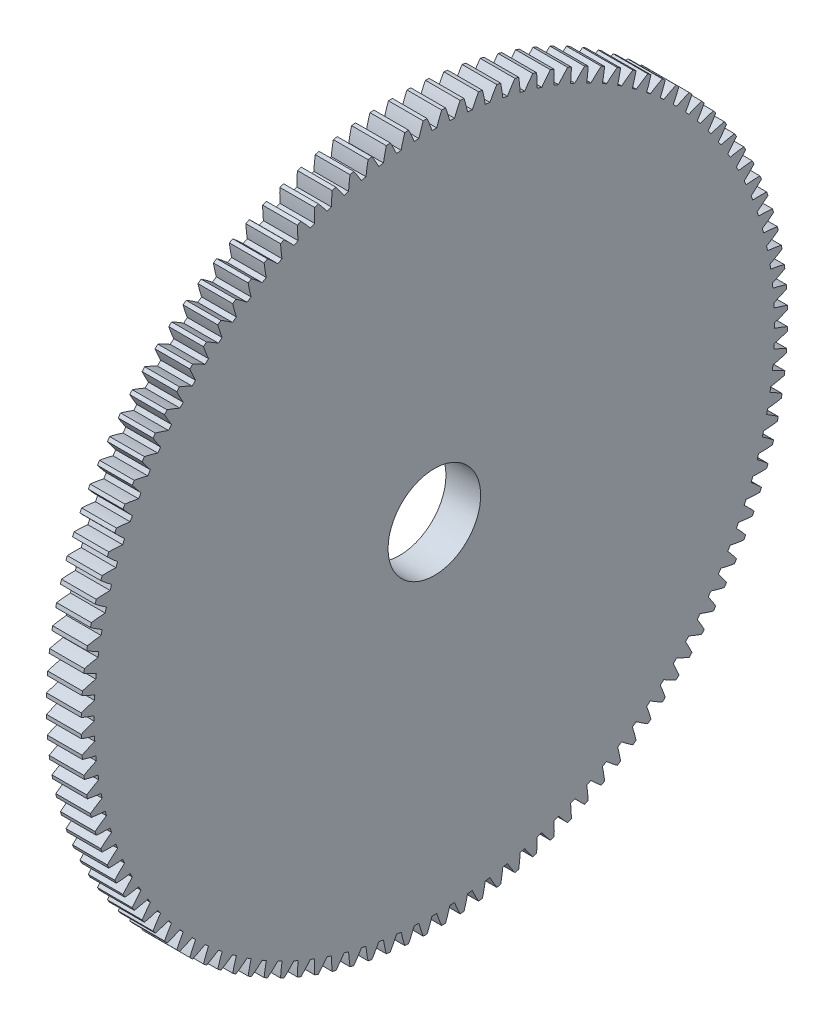
SolidWorks part; units mm, degrees
ref_plane "Plane1" through (0, 0, 0) normal (0, 0, 1) x (1, 0, 0)
ref_plane "Plane2" through (0, 0, 0) normal (0, 1, 0) x (1, 0, 0)
ref_plane "Plane3" through (0, 0, 0) normal (1, 0, 0) x (0, 0, -1)
sketch "HoldingSke" plane through (0, 0, 0) normal (0, 1, 0) x (1, 0, 0)
  line L0 (0, 0) -> (-1, -1.7321)
  line L1 (-15, 0) -> (100, 0) construction
  line L2 (0, 0) -> (-2.1039, 2.3779)
  line L3 (0, 0) -> (-11.863, 4.5341)
  line L4 (0, 0) -> (-4.318, 7.479)
  line L5 (0, 0) -> (-46.8476, -17.4728)
  line L6 (0, 0) -> (-2.4869, -1.6779)
  line L7 (-2.1039, 2.3779) -> (8.6586, 51.2059)
  line L8 (-76.2, 54.61) -> (-74.8, 54.61)
  line L9 (-71.009, 38.7566) -> (-53.1078, 45.2721)
  line L10 (-76.2, 71.12) -> (104.1128, 71.12)
  line L11 (0, 0) -> (-3, 0)
  line L12 (-76.2, 101.6) -> (-76.181, 101.6)
  line L13 (24.9733, 27.94) -> (52.9518, 28.4284)
  line L14 (24.9733, 27.94) -> (24.9743, 27.94)
  line L15 (24.9733, 27.94) -> (100.4006, 29.5858)
  line L16 (-63.627, -0.5) -> (-12.827, -0.5)
  circle A0 centre (0, 0) radius 4
  circle A1 centre (0, 0) radius 29.374
  circle A2 centre (0, 0) radius 37.5
  circle A3 centre (0, 0) radius 4
  dimension "Num_teeth" = 120
  dimension "Pitch_radius" = 180.3128
  dimension "Width" = 3
  dimension "Thickness" = 3
sketch "BasProSke" plane through (0, 0, 0) normal (0, 1, 0) x (1, 0, 0)
  line L0 (-10, 0) -> (60, 0) construction
  line L1 (0, 0) -> (0, 30.5)
  line L2 (0, 0) -> (3, 0)
  line L3 (3, 0) -> (3, 30.5)
  line L4 (3, 30.5) -> (0, 30.5)
  dimension "Thickness" = 3
  dimension "Diameter" = 61
revolve "Base-Revolve" add sketch "BasProSke" angle 360 about L0
sketch "TooCutSke" plane through (0, 0, 0) normal (1, 0, 0) x (0, 0, -1)
  line L1 (0, 0) -> (0, 107) construction
  line L2 (0, 0) -> (-0.4259, 29.997) construction
  line L3 (0, 0) -> (-1.5705, 59.9751) construction
  line L4 (-0.4259, 29.997) -> (-0.7853, 29.9876) construction
  arc A0 (0.2052, 29.3733) -> (-0.2052, 29.3733) centre (0, 0) ccw
  arc A1 (0.6411, 30.5187) -> (-0.6411, 30.5187) centre (0, 0) ccw
  circle A2 centre (0, 0) radius 30 construction
  circle A3 centre (0, 0) radius 28.1908 construction
  arc A4 (-0.2052, 29.3733) -> (-0.6411, 30.5187) centre (-11.6236, 25.6829) ccw
  arc A5 (0.6411, 30.5187) -> (0.2052, 29.3733) centre (11.6236, 25.6829) ccw
extrude "ToothCut" cut sketch "TooCutSke" along normal through all
fillet "Breaks" [suppressed] radius 0.01 tangent propagation no
fillet "RootFillets" [suppressed] radius 0.126
pattern_circular "TeethCuts" count 120 every 3 about axis through (-10, 0, 0) along (1, 0, 0) of "ToothCut", "RootFillets", "Breaks"
sketch "HubNeaOneSke" plane through (0, 0, 0) normal (-1, 0, 0) x (0, 0, 1)
  circle A0 centre (0, 0) radius 29.374
  dimension "Diameter" = 58.748
extrude "HubNearOne" [suppressed] add sketch "HubNeaOneSke" along normal blind 47.0001
sketch "HubNeaBotSke" plane through (0, 0, 0) normal (-1, 0, 0) x (0, 0, 1)
  circle A0 centre (0, 0) radius 29.374
  dimension "Diameter" = 58.748
extrude "HubNearBoth" [suppressed] add sketch "HubNeaBotSke" along normal blind 23.5
ref_plane "FarPln" through (3, 0, 0) normal (1, 0, 0) x (0, 0, -1)
sketch "HubFarSke" plane through (3, 0, 0) normal (1, 0, 0) x (0, 0, -1)
  circle A0 centre (0, 0) radius 29.374
  dimension "Diameter" = 58.748
extrude "HubFar" [suppressed] add sketch "HubFarSke" along normal blind 23.5
sketch "BorSke" plane through (0, 0, 0) normal (1, 0, 0) x (0, 0, -1)
  circle A0 centre (0, 0) radius 4
  dimension "Diameter" = 8
extrude "Bore" cut sketch "BorSke" along normal mid plane 100.0001
sketch "KeySke" plane through (0, 0, 0) normal (1, 0, 0) x (0, 0, -1)
  line L0 (-1.5, 0) -> (-1.5, 5.4)
  line L1 (-1.5, 5.4) -> (1.5, 5.4)
  line L2 (1.5, 5.4) -> (1.5, 0)
  line L3 (0, 0) -> (0, 34) construction
  line L4 (-1.5, 0) -> (1.5, 0)
  dimension "Width" = 3
extrude "Keyway" [suppressed] cut sketch "KeySke" along normal mid plane 100.0001
pattern_circular "Keyway2" [suppressed] count 2 every 90 about axis through (-10, 0, 0) along (1, 0, 0) reverse direction yes
equation "' \"Module@HoldingSke\" = 6.35"
equation "' \"Num_teeth@HoldingSke\" = 12"
equation "' \"Ap@HoldingSke\" =  20"
equation "' \"Ap@HoldingSke\" = 20"
equation "' \"Width@HoldingSke\" = 0.5 * 25.4"
equation "' \"Hub_dia@HoldingSke\"= 1 * 25.4"
equation "' \"Hub_dia@HoldingSke\" = 1 * 25.4"
equation "' \"Overall_len@HoldingSke\" = 1.0 * 25.4"
equation "' \"Bore@HoldingSke\" = 0.75 * 25.4"
equation "' \"T_dim@HoldingSke\" = 0.1 * 25.4"
equation "' \"Width@KeySke\" = 0.25 * 25.4"
equation "' \"Show_teeth@HoldingSke\" = 13"
equation "' \"Backlash@HoldingSke\" = 0.009 * 25.4"
equation "' \"Addendum_fac@HoldingSke\" = 1.0"
equation "' \"Dedendum_fac@HoldingSke\" = 1.25"
equation "' \"Dedendum_add@HoldingSke\" = 0.00005 * 25.4"
equation "' \"Clearance_fac@HoldingSke\" = 0.25"
equation "\"Pitch@HoldingSke\" = 1 / \"Module@HoldingSke\""
equation "\"Overcut_dia@TooCutSke\" = (\"Num_teeth@HoldingSke\" + 2 * \"Addendum_fac@HoldingSke\") / \"Pitch@HoldingSke\" + 0.002 * 25.4"
equation "\"Pitch_dia@TooCutSke\" = \"Num_teeth@HoldingSke\" / \"Pitch@HoldingSke\""
equation "\"Base_dia@TooCutSke\" = \"Num_teeth@HoldingSke\" / \"Pitch@HoldingSke\" * cos((\"Ap@HoldingSke\"  * 3.14159265 / 180))"
equation "\"Root_dia@TooCutSke\" = (\"Num_teeth@HoldingSke\" + 2) / \"Pitch@HoldingSke\" - 2 * (\"Addendum_fac@HoldingSke\" + \"Dedendum_fac@HoldingSke\") / \"Pitch@HoldingSke\" - \"Dedendum_add@HoldingSke\" * 2"
equation "\"Half_ang@TooCutSke\" = 180 / \"Num_teeth@HoldingSke\""
equation "\"Half_CT@TooCutSke\" = \"Num_teeth@HoldingSke\" / \"Pitch@HoldingSke\" * sin((3.14159265 / 2 / \"Num_teeth@HoldingSke\")) / 2 - 7 * \"Backlash@HoldingSke\" / 4"
equation "\"Flank_rad@TooCutSke\" = \"Num_teeth@HoldingSke\" / \"Pitch@HoldingSke\" / 5"
equation "\"Radius@RootFillets\" = \"Clearance_fac@HoldingSke\" / \"Pitch@HoldingSke\" + \"Dedendum_add@HoldingSke\""
equation "\"Break_rad@Breaks\" = 0.02 / \"Pitch@HoldingSke\""
equation "\"Thickness@HoldingSke\" = \"Width@HoldingSke\""
equation "\"OAL@HoldingSke\" = \"Thickness@HoldingSke\""
equation "\"MHD@HoldingSke\" = (\"Num_teeth@HoldingSke\" + 2) / \"Pitch@HoldingSke\" - 2 * (\"Addendum_fac@HoldingSke\" + \"Dedendum_fac@HoldingSke\")  / \"Pitch@HoldingSke\" - \"Dedendum_add@HoldingSke\" * 2"
equation "\"MBD@HoldingSke\" = (\"Num_teeth@HoldingSke\" + 2) / \"Pitch@HoldingSke\" - 2 * (\"Addendum_fac@HoldingSke\" + \"Dedendum_fac@HoldingSke\")  / \"Pitch@HoldingSke\" - \"Dedendum_add@HoldingSke\" * 2 - 0.002 * 25.4"
equation "\"MHD@HoldingSke\" = ((sgn( \"MHD@HoldingSke\" - \"Hub_dia@HoldingSke\" )-1)*( \"MHD@HoldingSke\" - \"Hub_dia@HoldingSke\" ))/-2+ \"Hub_dia@HoldingSke\""
equation "\"MBD@HoldingSke\" = ((sgn( \"MBD@HoldingSke\" - \"Bore@HoldingSke\" )-1)*( \"MBD@HoldingSke\" - \"Bore@HoldingSke\" ))/-2+ \"Bore@HoldingSke\""
equation "\"OAL@HoldingSke\" = ((sgn( \"OAL@HoldingSke\" - \"Overall_len@HoldingSke\" )+1)*( \"OAL@HoldingSke\" - \"Overall_len@HoldingSke\" ))/2 + \"Overall_len@HoldingSke\" + 0.000002 * 25.4"
equation "\"Num_teeth@TeethCuts\" = int( \"Show_teeth@HoldingSke\" ) + 1"
equation "\"Num_teeth@TeethCuts\" = ((sgn( \"Num_teeth@TeethCuts\" - \"Num_teeth@HoldingSke\" )-1)*( \"Num_teeth@TeethCuts\" - \"Num_teeth@HoldingSke\" ))/-2+ \"Num_teeth@HoldingSke\""
equation "\"Num_teeth@TeethCuts\" = ((sgn( \"Num_teeth@TeethCuts\" - 2.0)+1)*( \"Num_teeth@TeethCuts\" - 2.0))/2 +2.0"
equation "\"Angle@TeethCuts\" = 360.0 / \"Num_teeth@HoldingSke\""
equation "\"Diameter@BasProSke\" = (\"Num_teeth@HoldingSke\" + 2 * \"Addendum_fac@HoldingSke\") / \"Pitch@HoldingSke\""
equation "\"Thickness@BasProSke\"  = \"Thickness@HoldingSke\""
equation "' \"Fillet_rad@BasProSke\" =  \"Thickness@HoldingSke\" * 0.05"
equation "' \"Fillet_rad@BasProSke\" = \"Thickness@HoldingSke\" * 0.05"
equation "\"MHD@HoldingSke\" = ((sgn( \"MHD@HoldingSke\" - \"Root_dia@TooCutSke\" )-1)*( \"MHD@HoldingSke\" - \"Root_dia@TooCutSke\" ))/-2+ \"Root_dia@TooCutSke\""
equation "\"Diameter@HubNeaOneSke\" = \"MHD@HoldingSke\""
equation "\"Length@HubNearOne\" = \"OAL@HoldingSke\" - \"Thickness@BasProSke\""
equation "\"Diameter@HubNeaBotSke\" = \"MHD@HoldingSke\""
equation "\"Length@HubNearBoth\" = ( \"OAL@HoldingSke\" - \"Thickness@BasProSke\" ) / 2.0"
equation "\"Thickness@FarPln\" = \"Thickness@BasProSke\""
equation "\"Diameter@HubFarSke\" = \"MHD@HoldingSke\""
equation "\"Length@HubFar\" = ( \"OAL@HoldingSke\" - \"Thickness@BasProSke\" ) / 2.0"
equation "\"Diameter@BorSke\" = \"MBD@HoldingSke\""
equation "\"D1@Bore\" = \"OAL@HoldingSke\" * 2.0"
equation "\"D1@Keyway\" = \"OAL@HoldingSke\" * 2.0"
equation "\"Offset@KeySke\" = \"T_dim@HoldingSke\" + \"MBD@HoldingSke\" / 2.0"
